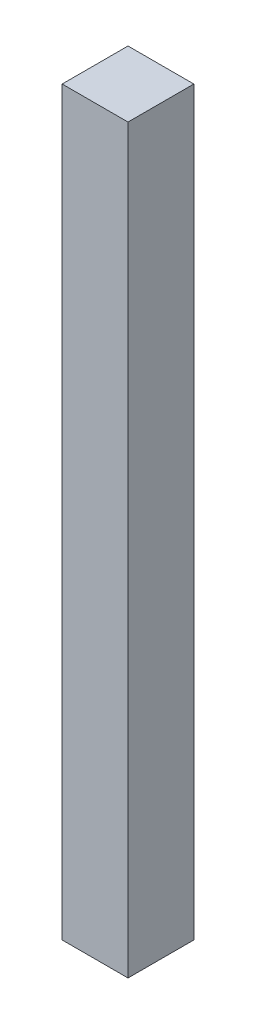
SolidWorks part; units mm, degrees
ref_plane "Front Plane" through (0, 0, 0) normal (0, 0, 1) x (1, 0, 0)
ref_plane "Top Plane" through (0, 0, 0) normal (0, 1, 0) x (1, 0, 0)
ref_plane "Right Plane" through (0, 0, 0) normal (1, 0, 0) x (0, 0, -1)
sketch "Sketch1" plane through (0, 0, 0) normal (0, 1, 0) x (1, 0, 0)
  line L1 (0, 0) -> (25.4, 0)
  line L2 (0, 0) -> (0, 25.4)
  line L3 (0, 25.4) -> (25.4, 25.4)
  line L4 (25.4, 0) -> (25.4, 25.4)
  dimension "D1" = 25.4
  dimension "D2" = 25.4
extrude "Boss-Extrude1" add sketch "Sketch1" along normal blind 609.6
sketch "Sketch3" plane through (0, 0, -25.4) normal (0, 0, -1) x (-1, 0, 0)
  line L0 (0, 609.6) -> (0, 0) construction
  line L1 (0, 466.3042) -> (-25.4, 466.3042)
  line L2 (0, 466.3042) -> (0, 609.6)
  line L3 (0, 609.6) -> (-25.4, 609.6)
  line L4 (-25.4, 466.3042) -> (-25.4, 609.6)
  line L6 (-25.4, 466.3042) -> (0, 466.3042) construction
extrude "Cut-Extrude1" [suppressed] cut sketch "Sketch3" against normal up to surface (25.4 mm away) up to face at (12.7, 304.8, 0)
sketch "Sketch4" [suppressed] plane through (0, 0, 0) normal (0, 0, 1) x (1, 0, 0)
  line L0 (0, 609.6) -> (0, 0) construction
  line L1 (0, 276.4933) -> (25.4, 276.4933)
  line L2 (0, 276.4933) -> (0, 609.6)
  line L3 (0, 609.6) -> (25.4, 609.6)
  line L4 (25.4, 276.4933) -> (25.4, 609.6)
  line L6 (0, 276.4933) -> (25.4, 276.4933) construction
extrude "Cut-Extrude2" [suppressed] cut sketch "Sketch4" against normal up to surface (430.6021 mm away) up to face at (12.7, 304.8, -25.4)
sketch "Sketch5" plane through (0, 0, -25.4) normal (0, 0, -1) x (-1, 0, 0)
  line L0 (0, 609.6) -> (0, 0) construction
  line L1 (0, 571.9407) -> (-25.4, 571.9407)
  line L2 (0, 571.9407) -> (0, 609.6)
  line L3 (0, 609.6) -> (-25.4, 609.6)
  line L4 (-25.4, 571.9407) -> (-25.4, 609.6)
extrude "Cut-Extrude3" cut sketch "Sketch5" against normal up to surface (25.4 mm away) up to face at (12.7, 304.8, 0)
sketch "Sketch6" [suppressed] plane through (0, 0, -25.4) normal (0, 0, -1) x (-1, 0, 0)
  line L0 (0, 609.6) -> (0, 0) construction
  line L1 (0, 553.696) -> (-25.4, 553.696)
  line L2 (0, 553.696) -> (0, 609.6)
  line L3 (0, 609.6) -> (-25.4, 609.6)
  line L4 (-25.4, 553.696) -> (-25.4, 609.6)
  line L6 (-25.4, 553.696) -> (0, 553.696) construction
extrude "Cut-Extrude4" [suppressed] cut sketch "Sketch6" against normal up to surface (25.4 mm away) up to face at (12.7, 285.9703, 0)
sketch "Sketch7" [suppressed] plane through (0, 0, 0) normal (0, 0, 1) x (1, 0, 0)
  line L0 (25.4, 609.6) -> (25.4, 0) construction
  line L1 (25.4, 422.1079) -> (0, 422.1079)
  line L2 (25.4, 422.1079) -> (25.4, 609.6)
  line L3 (25.4, 609.6) -> (0, 609.6)
  line L4 (0, 422.1079) -> (0, 609.6)
  line L8 (0, 422.1079) -> (25.4, 422.1079) construction
extrude "Cut-Extrude5" [suppressed] cut sketch "Sketch7" against normal up to surface (25.4 mm away) up to face at (12.7, 285.9703, -25.4)
sketch "Sketch8" [suppressed] plane through (0, 0, -25.4) normal (0, 0, -1) x (-1, 0, 0)
  line L0 (0, 609.6) -> (0, 0) construction
  line L1 (0, 319.3022) -> (-25.4, 319.3022)
  line L2 (0, 319.3022) -> (0, 609.6)
  line L3 (0, 609.6) -> (-25.4, 609.6)
  line L4 (-25.4, 319.3022) -> (-25.4, 609.6)
  line L6 (-25.4, 319.3022) -> (0, 319.3022) construction
extrude "Cut-Extrude6" [suppressed] cut sketch "Sketch8" against normal up to surface (25.4 mm away) up to face at (12.7, 285.9703, 0)
sketch "Sketch9" [suppressed] plane through (0, 0, 0) normal (0, 0, 1) x (1, 0, 0)
  line L0 (0, 609.6) -> (0, 0) construction
  line L1 (0, 329.8783) -> (25.4, 329.8783)
  line L2 (0, 329.8783) -> (0, 609.6)
  line L3 (0, 609.6) -> (25.4, 609.6)
  line L4 (25.4, 329.8783) -> (25.4, 609.6)
  line L6 (0, 329.8783) -> (25.4, 329.8783) construction
extrude "Cut-Extrude7" [suppressed] cut sketch "Sketch9" against normal up to surface (25.4 mm away) up to face at (12.7, 285.9703, -25.4)
sketch "Sketch10" [suppressed] plane through (25.4, 0, 0) normal (1, 0, 0) x (0, 0, -1)
  line L1 (25.4, 329.8783) -> (0, 329.8783)
  line L2 (25.4, 329.8783) -> (25.4, 0)
  line L3 (25.4, 0) -> (0, 0)
  line L4 (0, 329.8783) -> (0, 0)
extrude "Boss-Extrude2" [suppressed] add sketch "Sketch10" along normal blind 25.4
sketch "Sketch11" [suppressed] plane through (0, 0, -25.4) normal (0, 0, -1) x (-1, 0, 0)
  line L1 (0, 329.8783) -> (-50.8, 329.8783)
  line L2 (0, 329.8783) -> (0, 0)
  line L3 (0, 0) -> (-50.8, 0)
  line L4 (-50.8, 329.8783) -> (-50.8, 0)
extrude "Boss-Extrude3" [suppressed] add sketch "Sketch11" along normal blind 25.4
sketch "Sketch12" [suppressed] plane through (0, 0, 0) normal (0, 0, 1) x (1, 0, 0)
  line L1 (25.4, 319.3022) -> (0, 319.3022)
  line L2 (25.4, 319.3022) -> (25.4, 0)
  line L3 (25.4, 0) -> (0, 0)
  line L4 (0, 319.3022) -> (0, 0)
extrude "Boss-Extrude4" [suppressed] add sketch "Sketch12" along normal blind 25.4
sketch "Sketch13" [suppressed] plane through (25.4, 0, 0) normal (1, 0, 0) x (0, 0, -1)
  line L0 (-25.4, 0) -> (25.4, 0) construction
  line L1 (25.4, 319.3022) -> (-25.4, 319.3022)
  line L2 (25.4, 319.3022) -> (25.4, 0)
  line L3 (25.4, 0) -> (-25.4, 0)
  line L4 (-25.4, 319.3022) -> (-25.4, 0)
  line L5 (-25.4, 0) -> (-25.4, 319.3022) construction
extrude "Boss-Extrude5" [suppressed] add sketch "Sketch13" along normal blind 25.4
sketch "Sketch14" [suppressed] plane through (0, 0, -25.4) normal (0, 0, -1) x (-1, 0, 0)
  line L0 (-25.4, 422.1079) -> (-25.4, 0) construction
  line L1 (-25.4, 422.1079) -> (0, 422.1079)
  line L2 (-25.4, 422.1079) -> (-25.4, 0)
  line L3 (-25.4, 0) -> (0, 0)
  line L4 (0, 422.1079) -> (0, 0)
extrude "Boss-Extrude6" [suppressed] add sketch "Sketch14" along normal blind 25.4
sketch "Sketch15" [suppressed] plane through (25.4, 0, 0) normal (1, 0, 0) x (0, 0, -1)
  line L1 (50.8, 422.1079) -> (0, 422.1079)
  line L2 (50.8, 422.1079) -> (50.8, 0)
  line L3 (50.8, 0) -> (0, 0)
  line L4 (0, 422.1079) -> (0, 0)
extrude "Boss-Extrude7" [suppressed] add sketch "Sketch15" along normal blind 25.4
sketch "Sketch16" plane through (0, 0, 0) normal (0, 0, 1) x (1, 0, 0)
  line L1 (25.4, 571.9407) -> (0, 571.9407)
  line L2 (25.4, 571.9407) -> (25.4, 0)
  line L3 (25.4, 0) -> (0, 0)
  line L4 (0, 571.9407) -> (0, 0)
extrude "Boss-Extrude8" add sketch "Sketch16" along normal blind 25.4
sketch "Sketch17" plane through (25.4, 0, 0) normal (1, 0, 0) x (0, 0, -1)
  line L1 (25.4, 571.9407) -> (-25.4, 571.9407)
  line L2 (25.4, 571.9407) -> (25.4, 0)
  line L3 (25.4, 0) -> (-25.4, 0)
  line L4 (-25.4, 571.9407) -> (-25.4, 0)
extrude "Boss-Extrude9" add sketch "Sketch17" along normal blind 25.4
sketch "Sketch18" [suppressed] plane through (0, 0, -25.4) normal (0, 0, -1) x (-1, 0, 0)
  line L1 (0, 276.4933) -> (-25.4, 276.4933)
  line L2 (0, 276.4933) -> (0, 0)
  line L3 (0, 0) -> (-25.4, 0)
  line L4 (-25.4, 276.4933) -> (-25.4, 0)
extrude "Boss-Extrude10" [suppressed] add sketch "Sketch18" along normal blind 25.4
sketch "Sketch19" [suppressed] plane through (25.4, 0, 0) normal (1, 0, 0) x (0, 0, -1)
  line L1 (50.8, 276.4933) -> (0, 276.4933)
  line L2 (50.8, 276.4933) -> (50.8, 0)
  line L3 (50.8, 0) -> (0, 0)
  line L4 (0, 276.4933) -> (0, 0)
extrude "Boss-Extrude11" [suppressed] add sketch "Sketch19" along normal blind 25.4
sketch "Sketch22" [suppressed] plane through (25.4, 0, 0) normal (1, 0, 0) x (0, 0, -1)
  line L1 (0, 553.696) -> (25.4, 553.696)
  line L2 (0, 553.696) -> (0, 0)
  line L3 (0, 0) -> (25.4, 0)
  line L4 (25.4, 553.696) -> (25.4, 0)
extrude "Boss-Extrude14" [suppressed] add sketch "Sketch22" along normal blind 25.4
sketch "Sketch23" [suppressed] plane through (0, 0, -25.4) normal (0, 0, -1) x (-1, 0, 0)
  line L1 (-50.8, 553.696) -> (0, 553.696)
  line L2 (-50.8, 553.696) -> (-50.8, 0)
  line L3 (-50.8, 0) -> (0, 0)
  line L4 (0, 553.696) -> (0, 0)
extrude "Boss-Extrude15" [suppressed] add sketch "Sketch23" along normal blind 25.4
sketch "Sketch24" [suppressed] plane through (0, 0, 0) normal (0, 0, 1) x (1, 0, 0)
  line L0 (25.4, 466.3042) -> (25.4, 0) construction
  line L1 (0, 466.3042) -> (25.4, 466.3042)
  line L2 (0, 466.3042) -> (0, 0)
  line L3 (0, 0) -> (25.4, 0)
  line L4 (25.4, 466.3042) -> (25.4, 0)
extrude "Boss-Extrude16" [suppressed] add sketch "Sketch24" along normal blind 25.4
sketch "Sketch25" [suppressed] plane through (25.4, 0, 0) normal (1, 0, 0) x (0, 0, -1)
  line L1 (-25.4, 0) -> (25.4, 0)
  line L2 (-25.4, 0) -> (-25.4, 466.3042)
  line L3 (-25.4, 466.3042) -> (25.4, 466.3042)
  line L4 (25.4, 0) -> (25.4, 466.3042)
extrude "Boss-Extrude17" [suppressed] add sketch "Sketch25" along normal blind 25.4
sketch "Sketch26" [suppressed] plane through (0, 329.8783, 0) normal (0, 1, 0) x (1, 0, 0)
  line L0 (0, 50.8) -> (50.8, 50.8) construction
  line L1 (50.8, 0) -> (25.4, 0)
  line L2 (50.8, 0) -> (50.8, 50.8)
  line L4 (25.4, 0) -> (25.4, 25.4)
  line L5 (0, 50.8) -> (0, 0) construction
  line L6 (50.8, 50.8) -> (0, 50.8)
  line L8 (25.4, 25.4) -> (0, 25.4)
  line L9 (0, 50.8) -> (0, 25.4)
  dimension "D1" = 25.4
  dimension "D2" = 25.4
extrude "Cut-Extrude8" [suppressed] cut sketch "Sketch26" against normal up to surface (329.8783 mm away)
